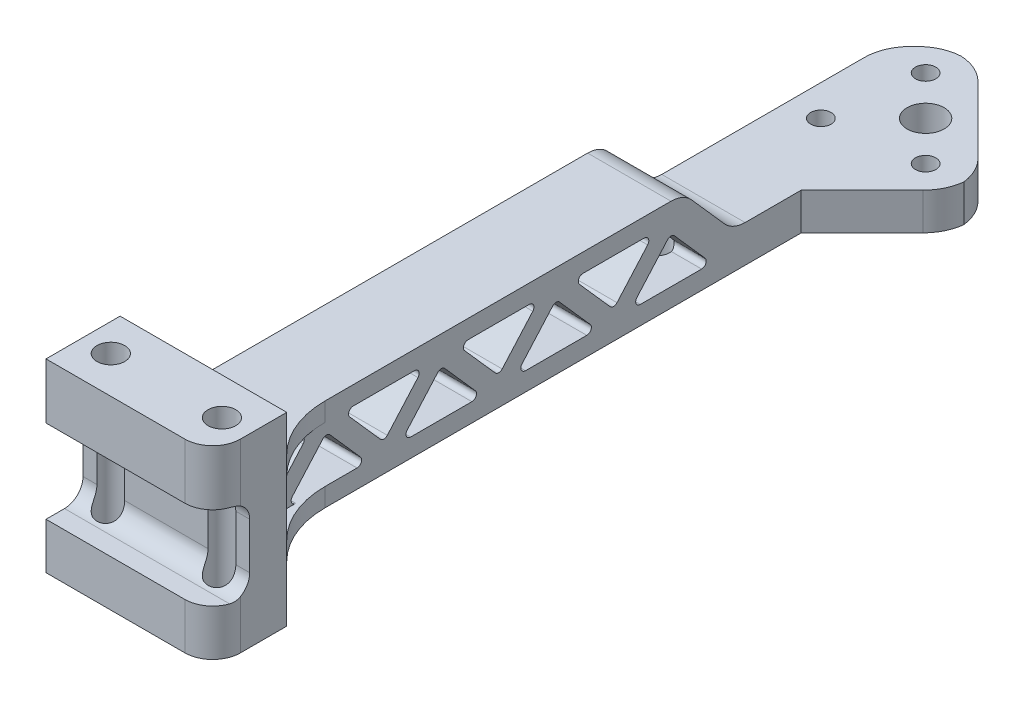
SolidWorks part; units mm, degrees
material "ABS PC"
ref_plane "Front Plane" through (0, 0, 0) normal (0, 0, 1) x (1, 0, 0)
ref_plane "Top Plane" through (0, 0, 0) normal (0, 1, 0) x (1, 0, 0)
ref_plane "Right Plane" through (0, 0, 0) normal (1, 0, 0) x (0, 0, -1)
sketch "Sketch1" plane through (0, 0, 0) normal (0, 1, 0) x (1, 0, 0)
  line L0 (0, 90.435) -> (0, 0)
  line L1 (0, 0) -> (15, 0)
  line L2 (18, 3) -> (18, 8)
  line L3 (18, 8) -> (11.9289, 14.0711)
  line L4 (9, 21.1421) -> (9, 72.565)
  line L5 (9, 72.565) -> (9, 86) construction
  line L6 (3, 4) -> (15, 4) construction
  line L7 (0, 90.435) -> (3.3076, 93.7426)
  line L8 (3.3076, 93.7426) -> (6.9142, 93.7426)
  line L9 (6.9142, 93.7426) -> (17.0459, 83.6109)
  line L10 (17.0459, 83.6109) -> (17.0459, 80.6109)
  line L11 (17.0459, 80.6109) -> (9, 72.565)
  line L12 (9, 86) -> (13.2426, 81.7574) construction
  line L13 (4.7574, 90.2426) -> (9, 86) construction
  line L14 (9, 86) -> (3.3431, 80.3431) construction
  circle A0 centre (9, 86) radius 6 construction
  circle A1 centre (9, 86) radius 8 construction
  circle A2 centre (3, 4) radius 1.5
  circle A3 centre (15, 4) radius 1.5
  arc A4 (18, 3) -> (15, 0) centre (15, 3) cw
  circle A5 centre (13.2426, 81.7574) radius 1.1
  circle A6 centre (4.7574, 90.2426) radius 1.1
  circle A7 centre (3.3431, 80.3431) radius 1.1
  circle A8 centre (9, 86) radius 2
  arc A9 (11.9289, 14.0711) -> (9, 21.1421) centre (19, 21.1421) cw
  point P17 (18, 0)
  dimension "D8" = 3
  dimension "D9" = 3
  dimension "D11" = 16
  dimension "D12" = 12
  dimension "D14" = 90
  dimension "D16" = 2.2
  dimension "D21" = 4
  dimension "D24" = 10
  dimension "D1" = 18
  dimension "D2" = 8
  dimension "D3" = 12
  dimension "D4" = 3
  dimension "D5" = 4
  dimension "D6" = 45
  dimension "D7" = 9
  dimension "D10" = 82
  dimension "D13" = 45
  dimension "D15" = 90
  dimension "D17" = 3.5
  dimension "D18" = 45
  dimension "D19" = 3.5
  dimension "D20" = 3.5
  dimension "D22" = 4
  dimension "D23" = 3
extrude "Boss-Extrude1" add sketch "Sketch1" along normal blind 10
sketch "Sketch2" plane through (0, 0, 0) normal (-1, 0, 0) x (0, 0, 1)
  line L0 (-96.1782, 8) -> (2.5289, 8) construction
  line L1 (2.5289, 8) -> (2.5289, 7) construction
  line L2 (2.5289, 7) -> (-96.1782, 7) construction
  line L3 (-96.1782, 7) -> (-96.1782, 5) construction
  line L4 (-96.1782, 5) -> (2.5289, 5) construction
  line L5 (2.5289, 5) -> (2.5289, 3) construction
  line L6 (2.5289, 3) -> (-96.1782, 3) construction
  line L7 (-96.1782, 3) -> (-96.1782, 2) construction
  line L8 (-96.1782, 2) -> (2.5289, 2) construction
  line L9 (-90.435, 10) -> (0, 10) construction
  line L10 (-90.435, 0) -> (0, 0) construction
  line L11 (-8, 8) -> (-8, 2)
  line L12 (-8, 2) -> (-13.3, 2)
  line L13 (-13.3, 2) -> (-8, 8)
  line L14 (-19.5019, 8) -> (-10.6685, 8)
  line L15 (-10.6685, 8) -> (-15.0852, 3)
  line L16 (-15.0852, 3) -> (-19.5019, 8)
  line L17 (-25.7037, 2) -> (-16.8704, 2)
  line L18 (-16.8704, 2) -> (-21.2871, 7)
  line L19 (-21.2871, 7) -> (-25.7037, 2)
  line L20 (-23.0723, 8) -> (-27.489, 3)
  line L21 (-27.489, 3) -> (-31.9056, 8)
  line L22 (-31.9056, 8) -> (-23.0723, 8)
  line L23 (-35.476, 8) -> (-39.8927, 3)
  line L24 (-39.8927, 3) -> (-44.3094, 8)
  line L25 (-44.3094, 8) -> (-35.476, 8)
  line L26 (-47.8798, 8) -> (-52.2965, 3)
  line L27 (-52.2965, 3) -> (-56.7131, 8)
  line L28 (-56.7131, 8) -> (-47.8798, 8)
  line L29 (-33.6908, 7) -> (-38.1075, 2)
  line L30 (-29.2742, 2) -> (-33.6908, 7)
  line L31 (-38.1075, 2) -> (-29.2742, 2)
  line L32 (-46.0946, 7) -> (-50.5112, 2)
  line L33 (-41.6779, 2) -> (-46.0946, 7)
  line L34 (-50.5112, 2) -> (-41.6779, 2)
  line L35 (-58.4983, 7) -> (-62.915, 2)
  line L36 (-54.0817, 2) -> (-58.4983, 7)
  line L37 (-62.915, 2) -> (-54.0817, 2)
  line L38 (0, 10) -> (0, 0) construction
  line L39 (-77, 8) -> (-77, 2)
  line L40 (-77, 2) -> (-71.7, 8)
  line L41 (-71.7, 8) -> (-77, 8)
  dimension "D1" = 2
  dimension "D2" = 2
  dimension "D3" = 1
  dimension "D4" = 1
  dimension "D5" = 2
  dimension "D6" = 5.3
  dimension "D7" = 2
  dimension "D8" = 2
  dimension "D11" = 8
  dimension "D12" = 77
  dimension "D13" = 2
  dimension "D14" = 2
  dimension "D9" = 4
  dimension "D10" = 4
extrude "Cut-Extrude1" cut sketch "Sketch2" against normal up to next
sketch "Sketch3" plane through (9, 0, 0) normal (1, 0, 0) x (0, 0, -1)
  line L0 (8, 8) -> (21.1421, 8)
  line L1 (21.1421, 10) -> (21.1421, 6.8359) construction
  line L2 (21.1421, 8) -> (21.1421, 2)
  line L3 (21.1421, 2) -> (8, 2)
  line L4 (8, 2) -> (8, 8)
extrude "Cut-Extrude2" cut sketch "Sketch3" along normal blind 30
fillet "Fillet2" radius 0.5 29 edges at (4.5, 2, -13.3) (9, 2, -8) (4.5, 8, -10.6685) (4.5, 3, -15.0852) (4.5, 8, -19.5019) (4.5, 2, -16.8704) (4.5, 2, -25.7037) (4.5, 7, -21.2871) (4.5, 8, -23.0723) (4.5, 3, -27.489) (4.5, 8, -31.9056) (4.5, 7, -33.6908) (4.5, 2, -29.2742) (4.5, 2, -38.1075) (4.5, 8, -35.476) (4.5, 3, -39.8927) (4.5, 8, -44.3094) (4.5, 2, -50.5112) (4.5, 7, -46.0946) (4.5, 2, -41.6779) (4.5, 8, -47.8798) (4.5, 3, -52.2965) (4.5, 8, -56.7131) (4.5, 2, -54.0817) (4.5, 7, -58.4983) (4.5, 2, -62.915) (4.5, 8, -71.7) (6.7175, 2, -77) (6.7175, 8, -77)
sketch "Sketch6" plane through (0, 10, 0) normal (0, 1, 0) x (1, 0, 0)
  line L0 (18, 8) -> (0, 8)
  line L1 (0, 90.435) -> (0, 0) construction
  line L2 (0, 8) -> (0, 0)
  line L3 (0, 0) -> (15, 0) construction
  line L4 (18, 3) -> (18, 8) construction
  line L5 (0, 0) -> (15, 0)
  line L6 (18, 3) -> (18, 8)
  circle A0 centre (3, 4) radius 1.5 construction
  circle A1 centre (15, 4) radius 1.5 construction
  arc A2 (15, 0) -> (18, 3) centre (15, 3) ccw construction
  circle A3 centre (3, 4) radius 1.5
  circle A4 centre (15, 4) radius 1.5
  arc A5 (15, 0) -> (18, 3) centre (15, 3) ccw
extrude "Boss-Extrude2" add sketch "Sketch6" along normal blind 10
sketch "Sketch7" plane through (0, 0, 0) normal (-1, 0, 0) x (0, 0, 1)
  line L0 (0, 20) -> (0, 0) construction
  line L1 (0, 14) -> (-4, 14)
  line L2 (0, 14) -> (0, 5)
  line L3 (0, 5) -> (-4, 5)
  line L4 (-4, 14) -> (-4, 5)
  line L5 (-90.435, 0) -> (0, 0) construction
  line L6 (-8, 20) -> (0, 20) construction
  dimension "D1" = 5
  dimension "D2" = 4
  dimension "D3" = 6
extrude "Cut-Extrude3" cut sketch "Sketch7" against normal through all
sketch "Sketch8" plane through (0, 0, 0) normal (-1, 0, 0) x (0, 0, 1)
  line L0 (-8, 20) -> (-8, 10)
  line L1 (-8, 10) -> (-18, 10)
  line L2 (-90.435, 10) -> (-8, 10) construction
  line L3 (-18, 10) -> (-8, 20)
  dimension "D1" = 45
extrude "Boss-Extrude3" add sketch "Sketch8" against normal blind 10
sketch "Sketch9" plane through (0, 0, 0) normal (-1, 0, 0) x (0, 0, 1)
  line L0 (-77, 7.5) -> (-77, 3.3213) construction
  line L1 (-76.1253, 2.9903) -> (-72.4341, 7.169) construction
  line L2 (-72.8088, 8) -> (-76.5, 8) construction
  line L3 (-77, 7.5) -> (-77, 3.3213)
  line L4 (-76.1253, 2.9903) -> (-72.4341, 7.169)
  line L5 (-72.8088, 8) -> (-76.5, 8)
  arc A0 (-76.5, 8) -> (-77, 7.5) centre (-76.5, 7.5) ccw construction
  arc A1 (-77, 3.3213) -> (-76.1253, 2.9903) centre (-76.5, 3.3213) ccw construction
  arc A2 (-72.4341, 7.169) -> (-72.8088, 8) centre (-72.8088, 7.5) ccw construction
  arc A3 (-76.5, 8) -> (-77, 7.5) centre (-76.5, 7.5) ccw
  arc A4 (-77, 3.3213) -> (-76.1253, 2.9903) centre (-76.5, 3.3213) ccw
  arc A5 (-72.4341, 7.169) -> (-72.8088, 8) centre (-72.8088, 7.5) ccw
extrude "Boss-Extrude4" add sketch "Sketch9" against normal up to surface (9.2438 mm away) up to face at (11.9923, 5.8714, -75.5572)
sketch "Sketch10" plane through (0, 0, 0) normal (-1, 0, 0) x (0, 0, 1)
  line L0 (-59.8511, 10) -> (-65.1511, 4)
  line L1 (-90.435, 10) -> (-18, 10) construction
  line L2 (-65.1511, 4) -> (-96.4392, 4)
  line L3 (-96.4392, 4) -> (-96.4392, 10)
  line L4 (-96.4392, 10) -> (-59.8511, 10)
  line L5 (-58.8731, 6.5758) -> (-62.1809, 2.831) construction
  line L6 (-90.435, 0) -> (0, 0) construction
  dimension "D1" = 3
  dimension "D2" = 4
extrude "Cut-Extrude4" cut sketch "Sketch10" against normal through all
fillet "Fillet3" radius 2 2 edges at (9, 14, -4) (9, 5, -4)
chamfer "Chamfer1" distance 7 angle 50 1 edges at (10, 15, -13) first distance on face at (10, 12.5, -12.6958)
fillet "Fillet4" radius 2 3 edges at (5.8289, 10, -13.0503) (5.8289, 15.0503, -8) (14, 10, -8)
fillet "Fillet5" radius 3 2 edges at (4.5, 10, -59.8511) (4.5, 4, -65.1511)
fillet "Fillet7" radius 5 5 edges at (0, 2, -90.435) (3.3076, 2, -93.7426) (6.9142, 2, -93.7426) (17.0459, 2, -83.6109) (17.0459, 2, -80.6109)
sketch "Sketch12" plane through (0, 0, 0) normal (0, -1, 0) x (-1, 0, 0)
  line L0 (0, 88.364) -> (0, 0) construction
  circle A0 centre (-4.5, 61.5855) radius 1.25
  dimension "D2" = 2.5
  dimension "D1" = 4.5
  dimension "D3" = 32.15
extrude "Cut-Extrude5" cut sketch "Sketch12" against normal blind 6
